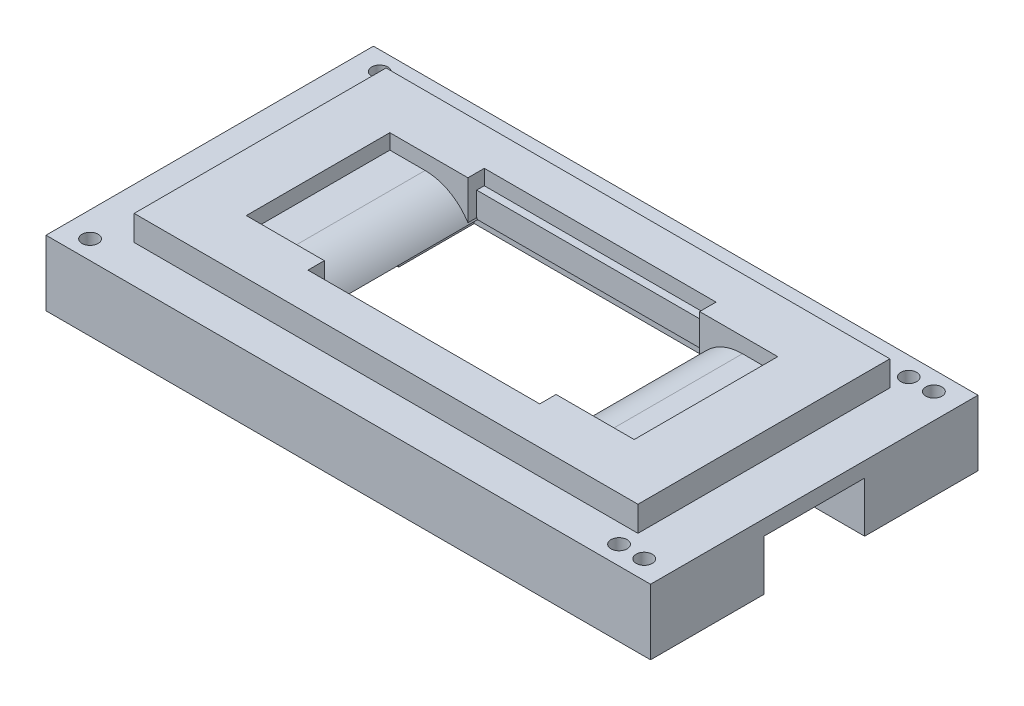
SolidWorks part; units mm, degrees
ref_plane "Front Plane" through (0, 0, 0) normal (0, 0, 1) x (1, 0, 0)
ref_plane "Top Plane" through (0, 0, 0) normal (0, 1, 0) x (1, 0, 0)
ref_plane "Right Plane" through (0, 0, 0) normal (1, 0, 0) x (0, 0, -1)
sketch "Sketch1" plane through (0, 0, 0) normal (0, 1, 0) x (1, 0, 0)
  line L0 (23, -14.25) -> (23, -17.5)
  line L7 (-50, 25) -> (50, 25)
  line L8 (-50, 25) -> (-50, -25)
  line L9 (-50, -25) -> (50, -25)
  line L10 (50, 25) -> (50, -25)
  line L11 (-50, 25) -> (50, -25) construction
  line L12 (-50, -25) -> (23, 11.5) construction
  line L15 (-38.5, 14.25) -> (-23, 14.25)
  line L16 (-38.5, 14.25) -> (-38.5, -14.25)
  line L17 (-38.5, -14.25) -> (-23, -14.25)
  line L18 (38.5, 14.25) -> (38.5, -14.25)
  line L19 (-38.5, 14.25) -> (38.5, -14.25) construction
  line L20 (-38.5, -14.25) -> (38.5, 14.25) construction
  line L21 (-23, 17.5) -> (23, 17.5)
  line L22 (-23, 17.5) -> (-23, 14.25)
  line L23 (-23, -17.5) -> (23, -17.5)
  line L24 (23, 17.5) -> (23, 14.25)
  line L25 (-23, 17.5) -> (23, -17.5) construction
  line L26 (-23, -17.5) -> (23, 17.5) construction
  line L27 (-23, -14.25) -> (-23, -17.5)
  line L28 (28.5, 14.25) -> (50, 25) construction
  line L29 (23, -14.25) -> (38.5, -14.25)
  line L30 (23, 14.25) -> (38.5, 14.25)
  point P0 (0, 0)
  point P1 (0, 0)
  point P2 (0, 0)
  point P6 (0, 0)
  point P17 (0, 0)
  dimension "D1" = 28.5
  dimension "D2" = 77
  dimension "D3" = 50
  dimension "D4" = 100
  dimension "D5" = 46
  dimension "D6" = 35
extrude "Boss-Extrude3" add sketch "Sketch1" along normal blind 2 contours L16 L17 L27 L23 L0 L29 L18 L30 L24 L21 L22 L15
extrude "Boss-Extrude4" add sketch "Sketch1<6>" along normal blind 5
sketch "Sketch1<6>" plane through (0, 0, 0) normal (0, 1, 0) x (1, 0, 0) same geometry as "Sketch1"
sketch "Sketch2" plane through (0, 0, 0) normal (0, -1, 0) x (1, 0, 0)
  line L0 (-60, 32.5) -> (-50, 25) construction
  line L1 (-60, 32.5) -> (60, 32.5)
  line L2 (-60, 32.5) -> (-60, -32.5)
  line L3 (-60, -32.5) -> (60, -32.5)
  line L4 (60, 32.5) -> (60, -32.5)
  line L5 (-60, 32.5) -> (60, -32.5) construction
  line L6 (-60, -32.5) -> (60, 32.5) construction
  line L7 (-55.7374, 27.7668) -> (-54.2626, 29.7332) construction
  line L8 (0, 0) -> (0, -0.0408) construction
  line L9 (-0.0011, 0) -> (0.0027, 0) construction
  circle A0 centre (-55, 28.75) radius 1.6
  circle A1 centre (55, 28.75) radius 1.6
  circle A2 centre (55, -28.75) radius 1.6
  circle A3 centre (-55, -28.75) radius 1.6
  circle A4 centre (50, 28.75) radius 1.6
  circle A5 centre (50, -28.75) radius 1.6
  point P0 (0, 0)
  point P14 (-55, 28.75)
  dimension "D3" = 3.2
  dimension "D4" = 105
  dimension "D5" = 3.2
  dimension "D1" = 65
  dimension "D2" = 120
extrude "Boss-Extrude5" add sketch "Sketch2" along normal blind 13
extrude "Boss-Extrude6" add sketch "Sketch2<2>" along normal blind 3
sketch "Sketch2<2>" plane through (0, 0, 0) normal (0, -1, 0) x (1, 0, 0) same geometry as "Sketch2"
sketch "Sketch7" plane through (0, 2, 0) normal (0, 1, 0) x (1, 0, 0)
  line L14 (-21.5, 16) -> (21.5, 16)
  line L15 (-21.5, 16) -> (-21.5, -16)
  line L16 (-21.5, -16) -> (21.5, -16)
  line L17 (21.5, 16) -> (21.5, -16)
  line L18 (-21.5, 16) -> (21.5, -16) construction
  line L19 (-21.5, -16) -> (21.5, 16) construction
  line L20 (23, 17.5) -> (-23, 17.5) construction
  line L21 (-23, -17.5) -> (23, -17.5) construction
  line L22 (23, 14.25) -> (23, 17.5) construction
  line L24 (-23, -14.25) -> (-23, -17.5) construction
  point P4 (0, 0)
  point P5 (0, 0)
  point P15 (0, 0)
  point P18 (-23, -15.875)
  dimension "D1" = 1.5
  dimension "D2" = 1.5
  dimension "D3" = 1.5
  dimension "D4" = 1.5
extrude "Cut-Extrude1" cut sketch "Sketch7" against normal up to next
fillet "Fillet1" radius 10 2 edges at (21.5, 2, 0) (-21.5, 2, 0)
sketch "Sketch8" plane through (0, -13, 0) normal (0, -1, 0) x (1, 0, 0)
  line L0 (-60, 32.5) -> (-60, -32.5) construction
  line L1 (-60, 10) -> (-21.5, 10)
  line L2 (-60, 10) -> (-60, -10)
  line L3 (-60, -10) -> (-21.5, -10)
  line L4 (-21.5, 10) -> (-21.5, -10)
  line L5 (-60, 10) -> (-21.5, -10) construction
  line L6 (-60, -10) -> (-21.5, 10) construction
  line L7 (-21.5, -16) -> (-21.5, 16) construction
  line L8 (0, 0) -> (0, 25.5611) construction
  line L9 (60, -10) -> (21.5, -10)
  line L10 (21.5, 10) -> (21.5, -10)
  line L11 (60, 10) -> (21.5, 10)
  line L12 (60, 10) -> (60, -10)
  point P4 (-40.75, 0)
  point P9 (-21.5, 0)
  point P10 (-21.5, 0)
  dimension "D1" = 20
extrude "Cut-Extrude2" cut sketch "Sketch8" against normal blind 10
sketch "Sketch9" plane through (0, -13, 0) normal (0, -1, 0) x (-1, 0, 0)
  line L1 (32.5, -25) -> (-32.5, -25)
  line L2 (32.5, -25) -> (32.5, 25)
  line L3 (32.5, 25) -> (-32.5, 25)
  line L4 (-32.5, -25) -> (-32.5, 25)
  line L5 (32.5, -25) -> (-32.5, 25) construction
  line L6 (32.5, 25) -> (-32.5, -25) construction
  point P4 (0, 0)
  dimension "D1" = 65
  dimension "D2" = 50
extrude "Cut-Extrude3" cut sketch "Sketch9" against normal blind 10
